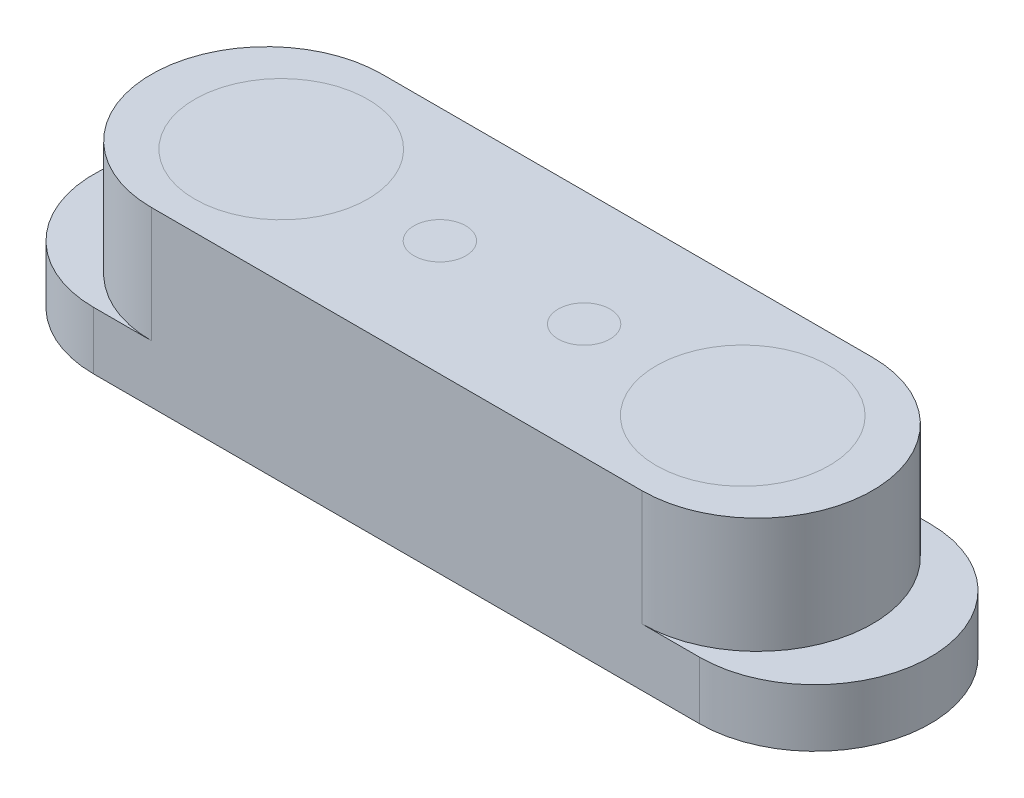
SolidWorks part; units mm, degrees
ref_plane "Front Plane" through (0, 0, 0) normal (0, 0, 1) x (1, 0, 0)
ref_plane "Top Plane" through (0, 0, 0) normal (0, 1, 0) x (1, 0, 0)
ref_plane "Right Plane" through (0, 0, 0) normal (1, 0, 0) x (0, 0, -1)
sketch "Sketch4" plane through (0, 0, 0) normal (0, 1, 0) x (1, 0, 0)
  line L0 (0, 0) -> (10.5, 0) construction
  line L1 (0, 2) -> (10.5, 2)
  line L2 (0, -2) -> (10.5, -2)
  arc A0 (0, 2) -> (0, -2) centre (0, 0) ccw
  arc A1 (10.5, -2) -> (10.5, 2) centre (10.5, 0) ccw
  point P3 (5.25, 0)
  point P8 (-2, 0)
  point P9 (12.5, 0)
  dimension "D1" = 14.5
  dimension "D2" = 4
extrude "Boss-Extrude2" add sketch "Sketch4" along normal blind 1
sketch "Sketch5" plane through (0, 1, 0) normal (0, 1, 0) x (1, 0, 0)
  line L0 (1, 0) -> (9.5, 0) construction
  line L1 (1, 2) -> (9.5, 2)
  line L2 (1, -2) -> (9.5, -2)
  arc A0 (1, 2) -> (1, -2) centre (1, 0) ccw
  arc A1 (9.5, -2) -> (9.5, 2) centre (9.5, 0) ccw
  point P2 (5.25, 0)
  point P7 (-1, 0)
  point P8 (11.5, 0)
  dimension "D1" = 12.5
  dimension "D2" = 4
  dimension "D3" = 1
  dimension "D4" = 0
extrude "Boss-Extrude3" add sketch "Sketch5" along normal blind 2
sketch "Sketch7" plane through (0, 3, 0) normal (0, 1, 0) x (1, 0, 0)
  circle A0 centre (1.25, 0) radius 1.5
  circle A1 centre (9.25, 0) radius 1.5
  circle A2 centre (4, 0) radius 0.45
  circle A3 centre (6.5, 0) radius 0.45
  dimension "D1" = 3
  dimension "D2" = 3
  dimension "D10" = 0.9
  dimension "D11" = 0.9
  dimension "D3" = 1.25
  dimension "D4" = 0
  dimension "D5" = 8
  dimension "D6" = 0
  dimension "D7" = 0
  dimension "D8" = 0
  dimension "D9" = 2.5
  dimension "D12" = 2.75
extrude "Cut-Extrude1" cut sketch "Sketch7" against normal blind 1
sketch "Sketch8" plane through (0, 2, 0) normal (0, 1, 0) x (1, 0, 0)
  circle A0 centre (1.25, 0) radius 1.5
  circle A1 centre (1.25, 0) radius 1.5 construction
  circle A2 centre (9.25, 0) radius 1.5
  circle A3 centre (9.25, 0) radius 1.5 construction
  dimension "D1" = 0
  dimension "D2" = 0
extrude "Boss-Extrude4" add sketch "Sketch8" along normal up to surface (1 mm away) separate body up to face at (1.25, 3, 1.5)
sketch "Sketch9" plane through (0, 2, 0) normal (0, 1, 0) x (1, 0, 0)
  circle A0 centre (4, 0) radius 0.45
  circle A1 centre (6.5, 0) radius 0.45
  circle A2 centre (4, 0) radius 0.45 construction
  circle A3 centre (6.5, 0) radius 0.45 construction
  dimension "D1" = 0
  dimension "D2" = 0
extrude "Boss-Extrude12" add sketch "Sketch9" along normal blind 1 and the other way blind 3.5 separate body
